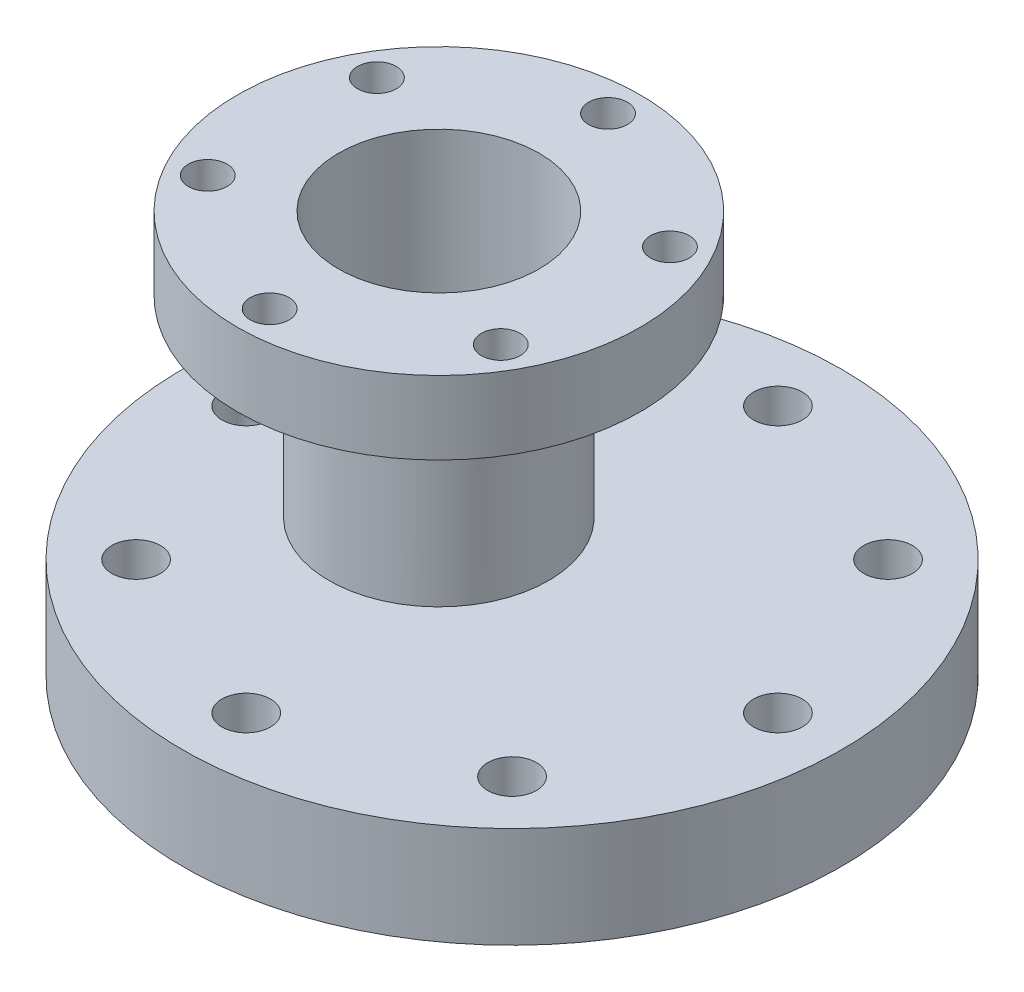
SolidWorks part; units mm, degrees
ref_plane "Front Plane" through (0, 0, 0) normal (0, 0, 1) x (1, 0, 0)
ref_plane "Top Plane" through (0, 0, 0) normal (0, 1, 0) x (1, 0, 0)
ref_plane "Right Plane" through (0, 0, 0) normal (1, 0, 0) x (0, 0, -1)
sketch "Sketch1" plane through (0, 0, 0) normal (0, 1, 0) x (1, 0, 0)
  circle A0 centre (0, 0) radius 19.05
  dimension "D1" = 38.1
extrude "Extrude1" add sketch "Sketch1" along normal mid plane 33.274
ref_plane "Plane1" through (0, 16.637, 0) normal (0, 1, 0) x (-1, 0, 0)
sketch "Sketch4" plane through (0, 16.637, 0) normal (0, 1, 0) x (-1, 0, 0)
  circle A0 centre (0, 0) radius 34.925
  dimension "D1" = 69.85
extrude "Extrude2" add sketch "Sketch4" along normal blind 12.7
ref_plane "Plane2" through (0, -16.637, 0) normal (0, -1, 0) x (1, 0, 0)
sketch "Sketch5" plane through (0, -16.637, 0) normal (0, -1, 0) x (1, 0, 0)
  point P0 (12.7, 0)
sketch "Sketch6" plane through (0, -16.637, 0) normal (0, -1, 0) x (1, 0, 0)
  circle A0 centre (12.7, 0) radius 57.15
  dimension "D1" = 114.3
extrude "Extrude3" add sketch "Sketch6" along normal blind 17.526
sketch "Sketch7" plane through (0, -16.637, 0) normal (0, -1, 0) x (1, 0, 0)
  circle A0 centre (0, 0) radius 17.399
  dimension "D1" = 34.798
extrude "Cut-Extrude1" cut sketch "Sketch7" against normal through all and the other way through all
ref_axis "Axis1" through (0, 69.0457, 0) along (0, -1, 0)
sketch "Sketch8" plane through (0, 16.637, 0) normal (0, 1, 0) x (-1, 0, 0)
  circle A0 centre (0, 29.337) radius 3.3655
extrude "Cut-Extrude2" cut sketch "Sketch8" along normal blind 12.7
pattern_circular "CirPattern1" count 6 over 360 about axis through (0, 69.0457, 0) along (0, -1, 0) of "Cut-Extrude2"
ref_axis "Axis2" through (12.7, -85.6827, 0) along (0, 1, 0)
sketch "Sketch9" plane through (0, -16.637, 0) normal (0, -1, 0) x (1, 0, 0)
  line L0 (0, 0) -> (12.7, 0)
  line L1 (12.7, 0) -> (12.7, 50.0096)
  circle A0 centre (12.7, 46.101) radius 4.2164
extrude "Cut-Extrude3" cut sketch "Sketch9" along normal blind 17.526 contours A0
pattern_circular "CirPattern2" count 8 over 360 about axis through (12.7, -85.6827, 0) along (0, 1, 0) of "Cut-Extrude3"
